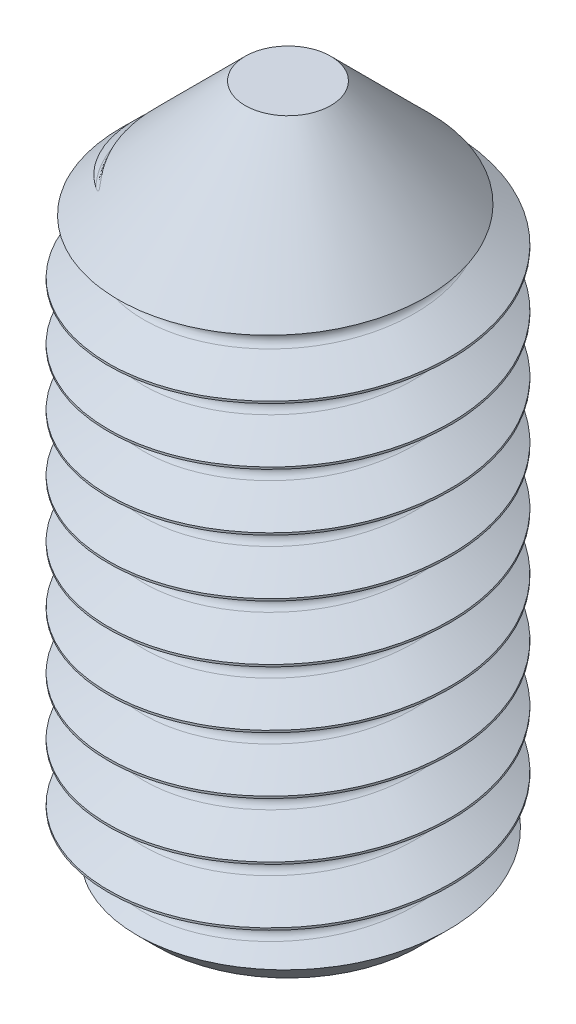
SolidWorks part; units mm, degrees
ref_plane "Front Plane" through (0, 0, 0) normal (0, 0, 1) x (1, 0, 0)
ref_plane "Top Plane" through (0, 0, 0) normal (0, 1, 0) x (1, 0, 0)
ref_plane "Right Plane" through (0, 0, 0) normal (1, 0, 0) x (0, 0, -1)
sketch "Sketch1" plane through (0, 0, 0) normal (0, 1, 0) x (1, 0, 0)
  circle A0 centre (0, 0) radius 3
  dimension "D1" = 6
extrude "Boss-Extrude1" add sketch "Sketch1" along normal mid plane 12
sketch "Sketch2" plane through (0, 0, 0) normal (0, 0, 1) x (1, 0, 0)
  line L0 (0.75, 6) -> (5.6582, 1.0918)
  line L1 (5.6582, 1.0918) -> (5.6582, -2.6418)
  line L2 (5.6582, -2.6418) -> (2.3, -6)
  line L3 (2.3, -6) -> (2.3, -11.4405)
  line L4 (2.3, -11.4405) -> (9.8714, -11.4405)
  line L5 (9.8714, -11.4405) -> (9.8714, 12.2044)
  line L6 (9.8714, 12.2044) -> (0.75, 12.2044)
  line L7 (0.75, 12.2044) -> (0.75, 6)
  line L8 (0, 0) -> (0, -3.1523) construction
  line L9 (3, 6) -> (-3, 6) construction
  line L10 (-3, -6) -> (3, -6) construction
  dimension "D1" = 1.5
  dimension "D2" = 4.6
  dimension "D3" = 135
  dimension "D4" = 135
revolve "Cut-Revolve1" cut sketch "Sketch2" angle 360 about L8
sketch "Sketch3" plane through (0, -6, 0) normal (0, -1, 0) x (1, 0, 0)
  line L1 (1.54, -0.8891) -> (1.54, 0.8891)
  line L2 (1.54, 0.8891) -> (0, 1.7782)
  line L3 (0, 1.7782) -> (-1.54, 0.8891)
  line L4 (-1.54, 0.8891) -> (-1.54, -0.8891)
  line L5 (-1.54, -0.8891) -> (0, -1.7782)
  line L6 (0, -1.7782) -> (1.54, -0.8891)
  circle A0 centre (0, 0) radius 1.54 construction
  dimension "D1" = 3.08
extrude "Cut-Extrude1" cut sketch "Sketch3" against normal blind 2.5
sketch "Sketch4" plane through (0, -6, 0) normal (0, -1, 0) x (1, 0, 0)
  circle A0 centre (0, 0) radius 3 construction
  circle A1 centre (0, 0) radius 3
curve "Helix/Spiral1" pitch 1 height 14.5 radius 3 centre (0, -6, 0) axis (0, 1, 0) start towards (0, 0, -1)
sketch "Sketch5" plane through (0, 0, 0) normal (0, 0, 1) x (1, 0, 0)
  line L1 (3.0226, -5.6359) -> (2.3817, -6.0059)
  line L2 (2.3817, -6.2558) -> (3.0226, -6.6259)
  line L3 (3.0226, -6.6259) -> (3.0226, -5.6359)
  circle A0 centre (2.7369, -6.1309) radius 0.2858 construction
  arc A1 (2.3817, -6.0059) -> (2.3817, -6.2558) centre (2.4539, -6.1309) ccw
  dimension "D2" = 0.1443
  dimension "D1" = 0.99
sweep "Cut-Sweep1" cut profiles "Sketch5" path "Helix/Spiral1" align with end faces yes
sketch "Sketch6" plane through (0, -6, 0) normal (0, -1, 0) x (1, 0, 0)
  circle A0 centre (0, 0) radius 1.7782
extrude "Cut-Extrude2" cut sketch "Sketch6" against normal blind 1.5 draft 75
sketch "Sketch7" plane through (0, 0, 0) normal (0, 0, 1) x (1, 0, 0)
  line L0 (-3, 2.8872) -> (-3, -6.3959) construction
